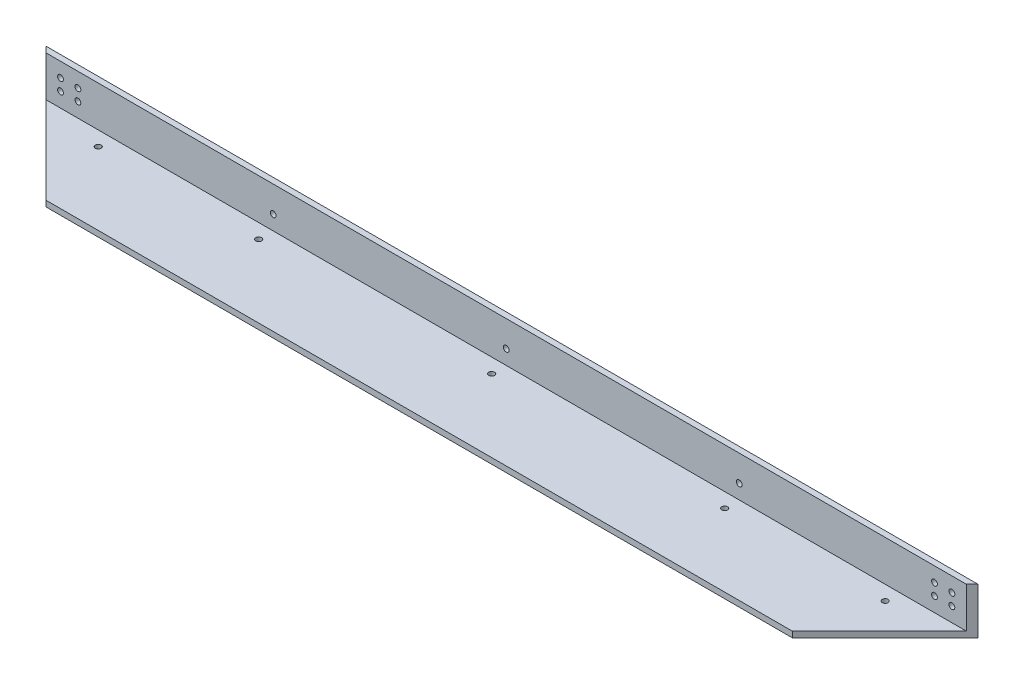
SolidWorks part; units mm, degrees
ref_plane "Front Plane" through (0, 0, 0) normal (0, 0, 1) x (1, 0, 0)
ref_plane "Top Plane" through (0, 0, 0) normal (0, 1, 0) x (1, 0, 0)
ref_plane "Right Plane" through (0, 0, 0) normal (1, 0, 0) x (0, 0, -1)
sketch "Sketch1" plane through (0, 0, 0) normal (1, 0, 0) x (0, 0, -1)
  line L0 (0, 0) -> (-50.8, 0)
  line L1 (-50.8, 0) -> (-50.8, 3.175)
  line L2 (-50.8, 3.175) -> (-3.175, 3.175)
  line L3 (-3.175, 3.175) -> (-3.175, 25.4)
  line L4 (-3.175, 25.4) -> (0, 25.4)
  line L5 (0, 25.4) -> (0, 0)
  dimension "LHeight" = 25.4
  dimension "LWidth" = 50.8
  dimension "LMaterialThickness" = 3.175
  dimension "D1" = 47.625
  dimension "D2" = 22.225
  dimension "D3" = 3.175
extrude "Boss-Extrude1" add sketch "Sketch1" along normal blind 510
chamfer "Chamfer6" distance 50.8 angle 45 1 edges at (510, 1.5875, 50.8)
chamfer "Chamfer7" distance 50.8 angle 45 1 edges at (0, 1.5875, 50.8)
sketch "SideHoles-Sketch2" plane through (0, 0, 0) normal (0, 0, -1) x (-1, 0, 0)
  line L0 (0, 0) -> (0, 25.4) construction
  line L1 (-510, 0) -> (0, 0) construction
  line L2 (-510, 0) -> (-510, 25.4) construction
  circle A0 centre (-498.8875, 17.4625) radius 1.5875
  circle A1 centre (-489.3625, 17.4625) radius 1.5875
  circle A2 centre (-20.6375, 17.4625) radius 1.5875
  circle A3 centre (-11.1125, 17.4625) radius 1.5875
  circle A4 centre (-11.1125, 11.1125) radius 1.5875
  circle A5 centre (-20.6375, 11.1125) radius 1.5875
  circle A6 centre (-489.3625, 11.1125) radius 1.5875
  circle A7 centre (-498.8875, 11.1125) radius 1.5875
  circle A8 centre (-382.5, 11.1125) radius 1.5875
  circle A9 centre (-255, 11.1125) radius 1.5875
  circle A10 centre (-127.5, 11.1125) radius 1.5875
  dimension "D5" = 3.175
  dimension "D1" = 11.1125
  dimension "D2" = 20.6375
  dimension "D3" = 11.1125
  dimension "D4" = 20.6375
  dimension "D6" = 7.9375
  dimension "D7" = 11.1125
  dimension "D8" = 127.5
  dimension "D9" = 127.5
  dimension "D10" = 127.5
sketch "BottomHoles-Sketch3" plane through (0, 0, 0) normal (0, -1, 0) x (1, 0, 0)
  line L0 (510, 0) -> (0, 0) construction
  circle A7 centre (39.6875, 11.1125) radius 1.5875
  circle A8 centre (470.3125, 11.1125) radius 1.5875
  circle A9 centre (127.5, 11.1125) radius 1.5875
  circle A10 centre (255, 11.1125) radius 1.5875
  circle A11 centre (382.5, 11.1125) radius 1.5875
  dimension "D5" = 3.175
  dimension "D2" = 39.6875
  dimension "D3" = 39.6875
  dimension "D4" = 11.1125
  dimension "D1" = 127.5
  dimension "D6" = 127.5
  dimension "D7" = 127.5
extrude "BottomHoles-Cut-Extrude1" cut sketch "BottomHoles-Sketch3" against normal through all
extrude "SideHoles-Cut-Extrude2" cut sketch "SideHoles-Sketch2" against normal through all
equation "\"LowerRailWidth\"= 2.00in"
equation "\"LowerRailHeight\"= 1.00in"
equation "\"RailThickness\"= .125in'Spec"
equation "\"SideRailHoleX1FromSide\"= \"HoleOffsetFromSide\""
equation "\"SideRailHoleX2FromSide\"= \"VSWidth\" - \"HoleOffsetFromEdge\" - \"RailThickness\"'Equals 20.6375"
equation "\"SideRailHoleY1FromEdge\"= \"HoleOffsetFromEdge\""
equation "\"FrontBackRailLength\"= 510mm"
equation "\"VSWidth\"= 1.25in'Spec"
equation "\"HoleOffsetFromEdge\"= \"RailThickness\" * 2.5"
equation "\"HoleOffsetFromSide\"= \"RailThickness\" * 3.5"
equation "\"SideRailHoleY2FromSide\"= \"HoleOffsetFromSide\""
equation "\"FasteningHoleDiameter\"= .125in"
equation "\"D1@Boss-Extrude1\"=\"FrontBackRailLength\""
equation "\"D1@Chamfer6\"=\"LowerRailWidth\""
equation "\"D1@Chamfer7\"=\"LowerRailWidth\""
equation "\"D1@SideHoles-Sketch2\" = \"SideRailHoleX1FromSide\""
equation "\"D2@SideHoles-Sketch2\" = \"SideRailHoleX2FromSide\""
equation "\"D3@SideHoles-Sketch2\" = \"SideRailHoleX1FromSide\""
equation "\"D4@SideHoles-Sketch2\" = \"SideRailHoleX2FromSide\""
equation "\"D5@SideHoles-Sketch2\" = \"FasteningHoleDiameter\""
equation "\"D6@SideHoles-Sketch2\" = \"SideRailHoleY1FromEdge\""
equation "\"D7@SideHoles-Sketch2\" = \"SideRailHoleY2FromSide\""
equation "\"LHeight@Sketch1\"=\"LowerRailHeight\""
equation "\"LWidth@Sketch1\"=\"LowerRailWidth\""
equation "\"24vPSUMountingHoleDistanceFromEdge\"= 33.5mm"
equation "\"24vPSUMountingHoleDistance\"= 150mm"
equation "\"24vPSUMountingHoleDiameter\"= 2.5mm"
equation "\"LowerCornerBlockWidth\"= \"LowerRailWidth\" - \"RailThickness\" * 2'Room for left front stepper"
equation "\"D2@BottomHoles-Sketch3\"=\"LowerCornerBlockX1FromSide\""
equation "\"D3@BottomHoles-Sketch3\"=\"LowerCornerBlockX1FromSide\""
equation "\"D4@BottomHoles-Sketch3\"=\"LowerCornerBlockY1FromSide\""
equation "\"D5@BottomHoles-Sketch3\"=\"FasteningHoleDiameter\""
equation "\"LowerCornerBlockX1FromSide\"= \"LowerCornerBlockWidth\" - \"HoleOffsetFromEdge\" + \"RailThickness\""
equation "\"LowerCornerBlockY1FromSide\"= \"HoleOffsetFromSide\""
equation "\"FrontOrBackEnclosureOffsets\"= \"FrontBackRailLength\" / 4"
equation "\"D1@BottomHoles-Sketch3\"=\"FrontOrBackEnclosureOffsets\""
equation "\"D6@BottomHoles-Sketch3\"=\"FrontOrBackEnclosureOffsets\""
equation "\"D7@BottomHoles-Sketch3\"=\"FrontOrBackEnclosureOffsets\""
equation "\"D8@SideHoles-Sketch2\"=\"FrontOrBackEnclosureOffsets\""
equation "\"D9@SideHoles-Sketch2\"=\"FrontOrBackEnclosureOffsets\""
equation "\"D10@SideHoles-Sketch2\"=\"FrontOrBackEnclosureOffsets\""
